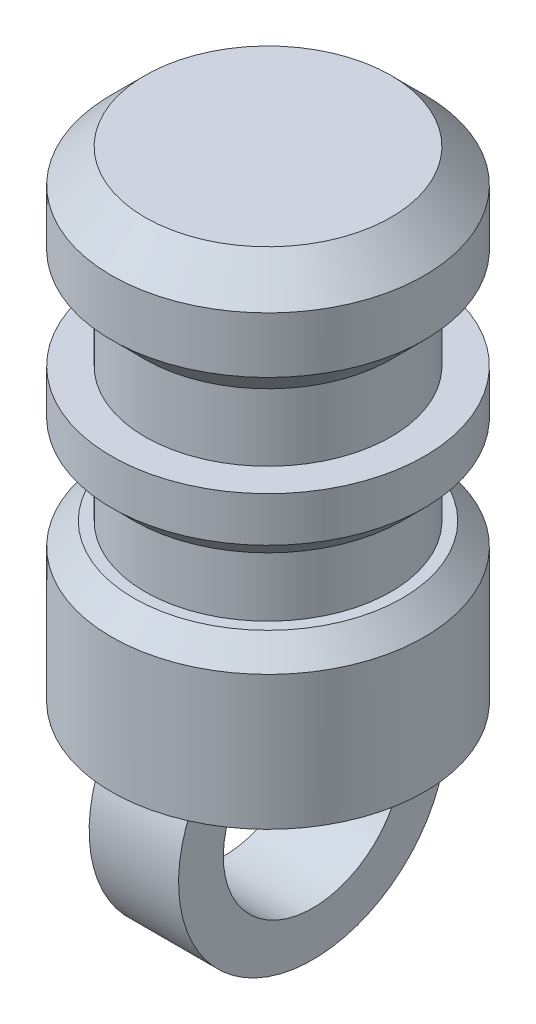
SolidWorks part; units mm, degrees
ref_plane "Alzado" through (0, 0, 0) normal (0, 0, 1) x (1, 0, 0)
ref_plane "Planta" through (0, 0, 0) normal (0, 1, 0) x (1, 0, 0)
ref_plane "Vista lateral" through (0, 0, 0) normal (1, 0, 0) x (0, 0, -1)
sketch "Croquis1" plane through (0, 0, 0) normal (0, 1, 0) x (1, 0, 0)
  line L1 (-18.35, -20) -> (18.35, -20)
  line L2 (-18.35, -20) -> (-18.35, 20)
  line L3 (-18.35, 20) -> (18.35, 20)
  line L4 (18.35, -20) -> (18.35, 20)
  line L5 (-18.35, -20) -> (18.35, 20) construction
  line L6 (-18.35, 20) -> (18.35, -20) construction
  circle A0 centre (0, 0) radius 4
  point P0 (0, 0)
  dimension "D3" = 8
  dimension "D1" = 36.7
  dimension "D2" = 40
extrude "Saliente-Extruir1" add sketch "Croquis1" along normal blind 7
sketch "Croquis2" plane through (0, 0, 0) normal (1, 0, 0) x (0, 0, -1)
  line L1 (4, 7) -> (0, 7) construction
  line L2 (0, 7) -> (0, 17.1204) construction
  line L3 (7, 7) -> (7, 12)
  line L4 (7, 12) -> (5.5, 12)
  line L5 (5.5, 12) -> (5.5, 15)
  line L6 (5.5, 15) -> (7, 15)
  line L7 (7, 15) -> (7, 18)
  line L8 (7, 18) -> (5.5, 18)
  line L9 (5.5, 18) -> (5.5, 21)
  line L10 (5.5, 21) -> (7, 22.5)
  line L11 (7, 22.5) -> (7, 24.5)
  line L12 (20, 7) -> (-20, 7) construction
  line L13 (4, 7) -> (4, 24.5)
  line L14 (4, 7) -> (-4, 7) construction
  line L15 (4, 7) -> (-4, 7) construction
  line L16 (7, 24.5) -> (4, 24.5)
  line L17 (4, 7) -> (7, 7)
  dimension "D1" = 5
  dimension "D2" = 3
  dimension "D3" = 3
  dimension "D4" = 3
  dimension "D5" = 1.5
  dimension "D6" = 7
  dimension "D7" = 5.5
  dimension "D8" = 2
revolve "Revolución1" add sketch "Croquis2" angle 360 about L2
chamfer "Chaflán1" distance 1 angle 45 2 edges at (0, 12, -7) (0, 15, -7)
sketch "Croquis3" plane through (0, 0, 0) normal (0, -1, 0) x (1, 0, 0)
  circle A0 centre (0, 0) radius 6.55
  dimension "D1" = 13.1
extrude "Cortar-Extruir1" cut sketch "Croquis3" against normal blind 2
sketch "Croquis5" plane through (0, 0, 20) normal (0, 0, 1) x (1, 0, 0)
  line L1 (-18.35, 7) -> (18.35, 7)
  line L2 (-18.35, 7) -> (-18.35, 0)
  line L3 (-18.35, 0) -> (18.35, 0)
  line L4 (18.35, 7) -> (18.35, 0)
extrude "Cortar-Extruir2" cut sketch "Croquis5" against normal through all
sketch "Croquis6" plane through (0, 7, 0) normal (0, -1, 0) x (1, 0, 0)
  circle A0 centre (0, 0) radius 7
extrude "Saliente-Extruir2" add sketch "Croquis6" along normal blind 2
sketch "Croquis7" plane through (0, 24.5, 0) normal (0, 1, 0) x (1, 0, 0)
  circle A0 centre (0, 0) radius 7
extrude "Saliente-Extruir3" add sketch "Croquis7" along normal blind 2
sketch "Croquis8" plane through (0, 0, 0) normal (1, 0, 0) x (0, 0, -1)
  line L0 (0, 5) -> (0, 2) construction
  line L2 (-7, 5) -> (7, 5) construction
  line L3 (-5.1962, 5) -> (0, 5)
  line L4 (2.6458, 5) -> (5.1962, 5)
  arc A1 (-2.6458, 5) -> (2.6458, 5) centre (0, 2) ccw
  arc A2 (-5.1962, 5) -> (5.1962, 5) centre (0, 2) ccw
  circle A3 centre (0, 2) radius 6 construction
  circle A4 centre (0, 2) radius 4 construction
  dimension "D1" = 8
  dimension "D3" = 3
  dimension "D2" = 2
extrude "Saliente-Extruir4" add sketch "Croquis8" along normal mid plane 4 contours L3 A2 L4 A1 region at (0, 4.85, 3.921)
chamfer "Chaflán2" distance 1.5 angle 45 1 edges at (0, 26.5, 7)
